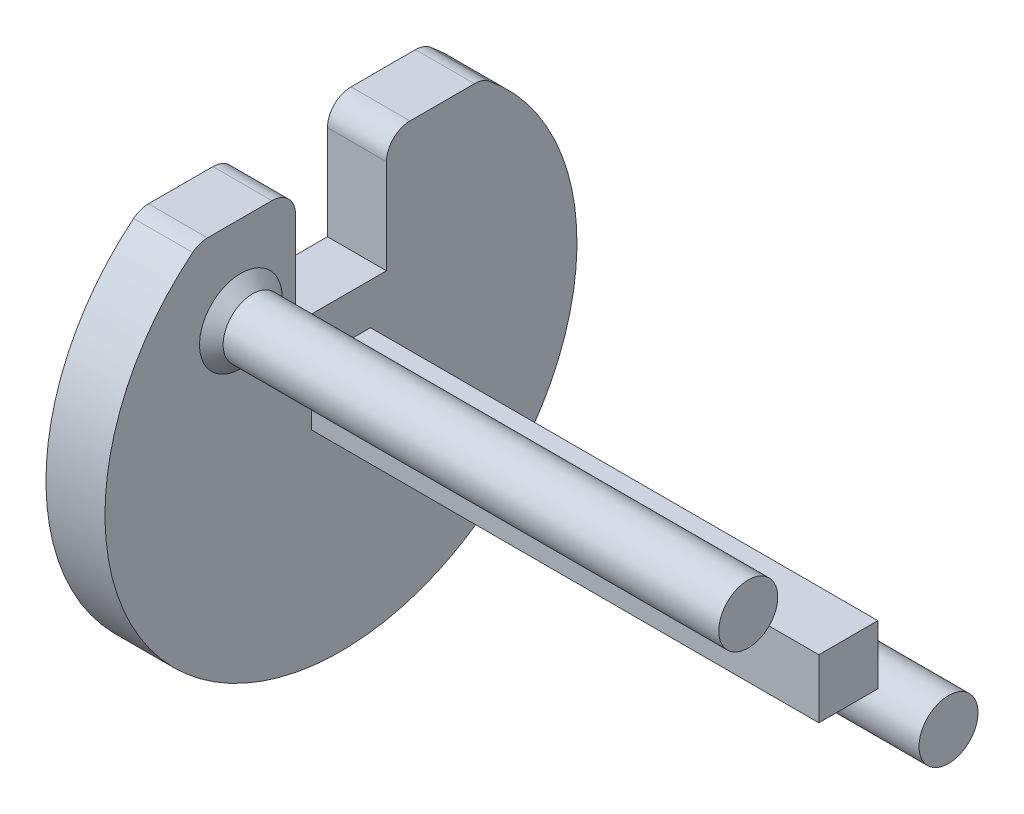
SolidWorks part; units mm, degrees
ref_plane "Front Plane" through (0, 0, 0) normal (0, 0, 1) x (1, 0, 0)
ref_plane "Top Plane" through (0, 0, 0) normal (0, 1, 0) x (1, 0, 0)
ref_plane "Right Plane" through (0, 0, 0) normal (1, 0, 0) x (0, 0, -1)
sketch "Sketch2" plane through (0, 0, 0) normal (1, 0, 0) x (0, 0, -1)
  circle A0 centre (0, 0) radius 20
  dimension "D1" = 40
extrude "Boss-Extrude2" add sketch "Sketch2" along normal blind 5
sketch "Sketch3" plane through (5, 0, 0) normal (1, 0, 0) x (0, 0, -1)
  line L1 (-2.5, -2.5) -> (2.5, -2.5)
  line L2 (-2.5, -2.5) -> (-2.5, 2.5)
  line L3 (-2.5, 2.5) -> (2.5, 2.5)
  line L4 (2.5, -2.5) -> (2.5, 2.5)
  line L5 (-2.5, -2.5) -> (2.5, 2.5) construction
  line L6 (-2.5, 2.5) -> (2.5, -2.5) construction
  point P0 (0, 0)
  dimension "D1" = 5
  dimension "D2" = 5
extrude "Boss-Extrude3" add sketch "Sketch3" along normal blind 43
sketch "Sketch4" plane through (5, 0, 0) normal (1, 0, 0) x (0, 0, -1)
  line L0 (8.4853, -8.4853) -> (-8.4853, 8.4853)
  line L1 (0, 0) -> (0, 50000) construction
  circle A1 centre (-8.4853, 8.4853) radius 2.5
  circle A2 centre (8.4853, -8.4853) radius 2.5
  point P4 (0, 0)
  dimension "D3" = 5
  dimension "D4" = 5
  dimension "D1" = 45
  dimension "D2" = 12
extrude "Boss-Extrude4" add sketch "Sketch4" along normal through all contours A1 | A2 region at (5, 9.4149, 10.7297) region at (5, -6.2409, -9.4149)
sketch "Sketch5" plane through (5, 0, 0) normal (1, 0, 0) x (0, 0, -1)
  line L0 (2.5, 2.5) -> (-2.5, 2.5) construction
  line L1 (-3.8523, 6) -> (3.8523, 6)
  line L2 (-3.8523, 6) -> (-3.8523, 20)
  line L3 (-3.8523, 20) -> (3.8523, 20)
  line L4 (3.8523, 6) -> (3.8523, 20)
  line L6 (-20, 20) -> (20, 20)
  line L7 (-20, 20) -> (-20, 16)
  line L8 (-20, 16) -> (20, 16)
  line L9 (20, 20) -> (20, 16)
  circle A0 centre (0, 0) radius 20 construction
  point P6 (0, 2.5)
  point P7 (0, 6)
  circle M7 centre (0, 0) radius 20
  dimension "D1" = 14
  dimension "D2" = 4
extrude "Cut-Extrude1" cut sketch "Sketch5" against normal through all contours L8 L2 M7 | L2 L8 L4 M7 | L4 L8 M7 | L8 L2 L1 L4 region at (5, 11, 0) region at (5, 17.3416, 6.8113) region at (5, 17.9394, 0) region at (5, 17.3416, -6.8113)
fillet "Fillet1" radius 2 4 edges at (2.5, 16, -12) (2.5, 16, -3.8523) (2.5, 16, 3.8523) (2.5, 16, 12)
chamfer "Chamfer1" distance 1 angle 45 2 edges at (5, -8.4853, -10.9853) (5, 8.4853, 5.9853)
